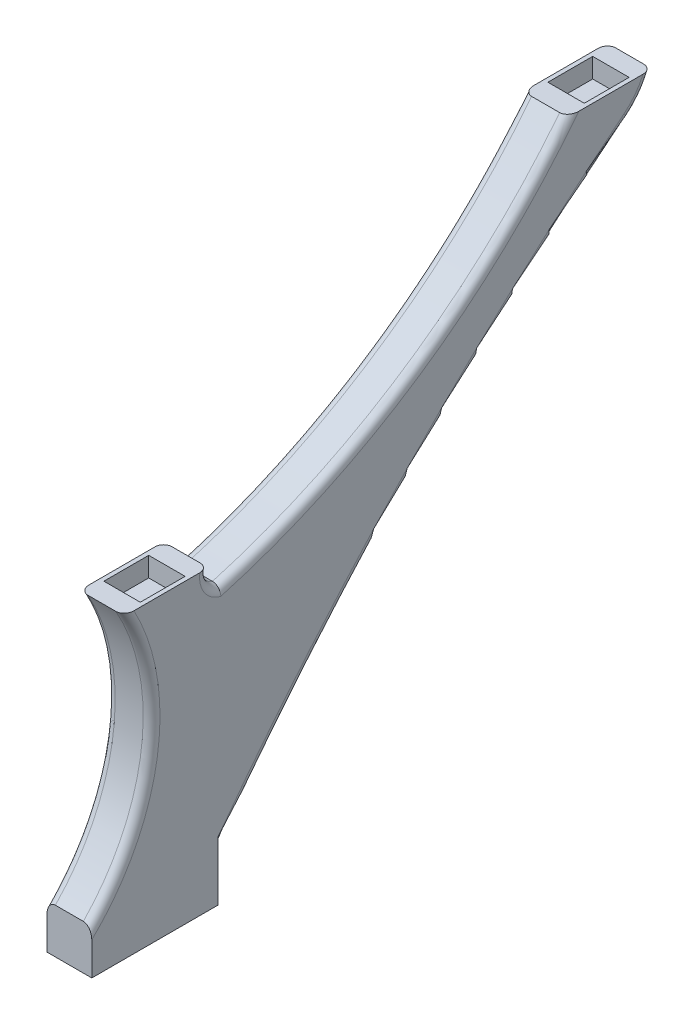
SolidWorks part; units mm, degrees
ref_plane "Ön Düzlem" through (0, 0, 0) normal (0, 0, 1) x (1, 0, 0)
ref_plane "Üst Düzlem" through (0, 0, 0) normal (0, 1, 0) x (1, 0, 0)
ref_plane "Sağ Düzlem" through (0, 0, 0) normal (1, 0, 0) x (0, 0, -1)
sketch "Çizim2" plane through (0, 0, 0) normal (1, 0, 0) x (0, 0, -1)
  line L1 (-14.4202, -67.8681) -> (30.5798, -67.8681)
  line L2 (185.5798, 97.1319) -> (155.5798, 97.1319)
  line L3 (-2.7961, 22.1319) -> (27.2039, 22.1319)
  arc A5 (-2.7961, 22.1319) -> (-14.4202, -67.8681) centre (-69.0884, -15.0567) cw
  arc A6 (30.5798, -67.8681) -> (177.3996, 85.9245) centre (684.5438, -545.2039) cw
  arc A7 (177.3996, 85.9245) -> (185.5798, 97.1319) centre (160.708, 106.6968) ccw
  arc A8 (27.2039, 22.1319) -> (31.65, 14.2094) centre (33.9512, 20.7097) ccw
  arc A9 (31.65, 14.2094) -> (155.5798, 97.1319) centre (-34.8216, 247.6224) ccw
  point P2 (8.0798, -67.8681)
  dimension "D3" = 75
  dimension "D6" = 45
  dimension "D1" = 30
  dimension "D2" = 30
  dimension "D4" = 90
  dimension "D5" = 200
extrude "Yükseklik-Ekstrüzyon1" add sketch "Çizim2" along normal blind 16
sketch "Çizim5" plane through (0, -67.8681, 0) normal (0, -1, 0) x (1, 0, 0)
  line L0 (8, 14.4202) -> (8, -30.5798) construction
  line L1 (16, 14.4202) -> (0, 14.4202) construction
  line L2 (16, -30.5798) -> (0, -30.5798) construction
  line L4 (0, 14.4202) -> (16, 14.4202)
  line L5 (0, 14.4202) -> (0, -30.5798)
  line L6 (0, -30.5798) -> (16, -30.5798)
  line L7 (16, 14.4202) -> (16, -30.5798)
  line L8 (0, 14.4202) -> (16, -30.5798) construction
  line L9 (0, -30.5798) -> (16, 14.4202) construction
  point P6 (8, -8.0798)
  dimension "D1" = 16
  dimension "D2" = 45
extrude "Yükseklik-Ekstrüzyon2" add sketch "Çizim5" along normal blind 16
fillet "Radyus4" radius 3 10 edges at (0, 90.9864, -182.2319) (16, 90.9864, -182.2319) (0, -24.7931, -6.2963) (16, -24.7931, -6.2963) (0, 13.8688, -98.9193) (16, 13.8688, -98.9193) (0, 17.335, -27.9379) (0, 45.9169, -100.1412) (16, 45.9169, -100.1412) (16, 17.335, -27.9379)
sketch "Çizim6" plane through (0, 97.1319, 0) normal (0, 1, 0) x (1, 0, 0)
  line L0 (8, 185.5798) -> (8, 155.5798) construction
  line L1 (14.5, 178.8621) -> (1.5, 178.8621)
  line L2 (14.5, 178.8621) -> (14.5, 162.8621)
  line L3 (14.5, 162.8621) -> (1.5, 162.8621)
  line L4 (1.5, 178.8621) -> (1.5, 162.8621)
  line L5 (14.5, 178.8621) -> (1.5, 162.8621) construction
  line L6 (14.5, 162.8621) -> (1.5, 178.8621) construction
  line L7 (13, 185.5798) -> (3, 185.5798) construction
  line L8 (13, 155.5798) -> (3, 155.5798) construction
  line L9 (0, 170.8621) -> (16, 170.8621) construction
  line L10 (0, 182.3349) -> (0, 159.3893) construction
  line L11 (16, 182.3349) -> (16, 159.3893) construction
  point P0 (8, 170.8621)
  dimension "D1" = 16
  dimension "D2" = 13
extrude "Kes-Ekstrüzyon1" cut sketch "Çizim6" against normal blind 7
sketch "Çizim7" plane through (0, 22.1319, 0) normal (0, 1, 0) x (1, 0, 0)
  line L0 (16, 12.3909) -> (0, 12.3909) construction
  line L1 (16, 24.1584) -> (16, 0.6234) construction
  line L2 (0, 24.1584) -> (0, 0.6234) construction
  line L3 (8, 27.2039) -> (8, -2.7961) construction
  line L4 (13, 27.2039) -> (3, 27.2039) construction
  line L5 (13, -2.7961) -> (3, -2.7961) construction
  line L7 (14.5, 20.3909) -> (1.5, 20.3909)
  line L8 (14.5, 20.3909) -> (14.5, 4.3909)
  line L9 (14.5, 4.3909) -> (1.5, 4.3909)
  line L10 (1.5, 20.3909) -> (1.5, 4.3909)
  line L11 (14.5, 20.3909) -> (1.5, 4.3909) construction
  line L12 (14.5, 4.3909) -> (1.5, 20.3909) construction
  point P12 (8, 12.3909)
  dimension "D1" = 16
  dimension "D2" = 13
extrude "Kes-Ekstrüzyon2" cut sketch "Çizim7" against normal blind 7
